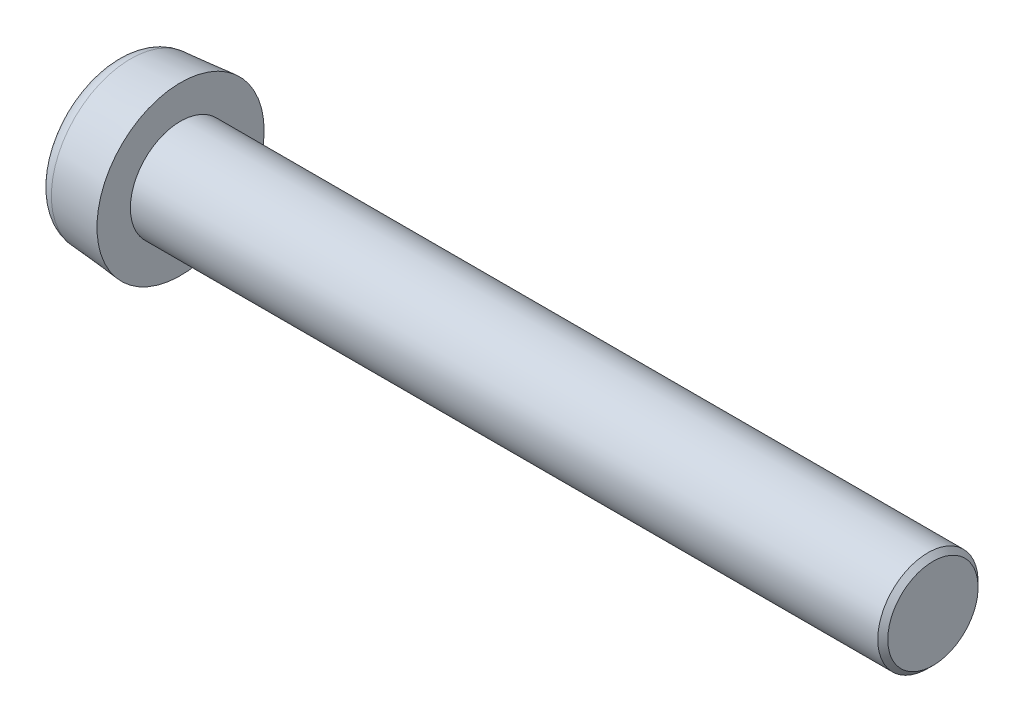
SolidWorks part; units mm, degrees
ref_plane "Front" through (0, 0, 0) normal (0, 0, 1) x (1, 0, 0)
ref_plane "Top" through (0, 0, 0) normal (0, 1, 0) x (1, 0, 0)
ref_plane "Right" through (0, 0, 0) normal (1, 0, 0) x (0, 0, -1)
ref_plane "Plane1" through (3.9, 0, 0) normal (1, 0, 0) x (0, 0, -1)
sketch "Sketch1" plane through (3.9, 0, 0) normal (1, 0, 0) x (0, 0, -1)
  circle A0 centre (0, 0) radius 5
  dimension "dk" = 10
extrude "BaseHead" add sketch "Sketch1" against normal blind 3.9 draft 5
sketch "Sketch2" plane through (3.9, 0, 0) normal (1, 0, 0) x (0, 0, -1)
  circle A0 centre (0, 0) radius 3
extrude "BaseBody" add sketch "Sketch2" along normal blind 45
cosmetic thread "ThreadCosmetic1" parameters "bb"=24, "THD_MINOR"=4.917
fillet "HeadFillet" [suppressed] radius 0.25
sketch "Sketch3" plane through (0, 0, 0) normal (1, 0, 0) x (0, 0, -1)
  line L1 (2.396, 0) -> (1.198, 2.075)
  line L2 (1.198, 2.075) -> (-1.198, 2.075)
  line L3 (-1.198, 2.075) -> (-2.396, 0)
  line L4 (-2.396, 0) -> (-1.198, -2.075)
  line L5 (-1.198, -2.075) -> (1.198, -2.075)
  line L6 (1.198, -2.075) -> (2.396, 0)
  circle A0 centre (0, 0) radius 2.075 construction
  dimension "B" = 4.15
extrude "HexagonSocket" cut sketch "Sketch3" along normal blind 2
sketch "Sketch4" plane through (2, 0, 0) normal (-1, 0, 0) x (0, 0, 1)
  line L0 (1.198, -2.075) -> (-1.198, -2.075) construction
  line L1 (-1.198, -2.075) -> (-2.396, 0) construction
  line L2 (-2.396, 0) -> (-1.198, 2.075) construction
  line L3 (2.396, 0) -> (1.198, -2.075) construction
  line L4 (1.198, 2.075) -> (2.396, 0) construction
  line L5 (-1.198, 2.075) -> (1.198, 2.075) construction
  line L6 (1.198, -2.075) -> (-1.198, -2.075)
  line L7 (-1.198, -2.075) -> (-2.396, 0)
  line L8 (-2.396, 0) -> (-1.198, 2.075)
  line L9 (2.396, 0) -> (1.198, -2.075)
  line L10 (1.198, 2.075) -> (2.396, 0)
  line L11 (-1.198, 2.075) -> (1.198, 2.075)
extrude "Cut-Extrude2" cut sketch "Sketch4" against normal blind 5 draft 60
fillet "TopFillet" radius 1 1 edges at (0, 0, -4.6588)
chamfer "Chamfer1" distance 0.3 angle 45 1 edges at (48.9, 0, -3)
sketch "Sketch5" plane through (0, 0, 0) normal (0, 0, 1) x (1, 0, 0)
  line L0 (48.6, 2.531) -> (48.8708, 3)
  line L1 (48.8708, 3) -> (48.8708, 3.5415)
  line L2 (48.8708, 3.5415) -> (48.3293, 3.5415)
  line L3 (48.3293, 3.5415) -> (48.3293, 3)
  line L4 (48.3293, 3) -> (48.6, 2.531)
  line L5 (0, 0) -> (26.2596, 0) construction
  line L6 (48.6, -3) -> (48.6, 3) construction
  dimension "D1" = 0.5415
  dimension "D2" = 6
revolve "Cut-Revolve10" [suppressed] cut sketch "Sketch5" angle 360 about L5
pattern_linear "LPattern10" [suppressed] count 37 spacing 0.6498 along (-1, 0, 0) of bodies 105
equation "\"D1@Plane1\" = \"K@BaseHead\""
equation "\"D2@Sketch5\" = \"d@Sketch2\""
equation "\"D1@Sketch5\" =  ( \"d@Sketch2\" - \"THD_MINOR@ThreadCosmetic1\" )  / 2"
equation "\"D3@LPattern10\" = \"D1@Sketch5\" * 1.2"
equation "\"D1@LPattern10\" = \"bb@ThreadCosmetic1\" / \"D3@LPattern10\""
